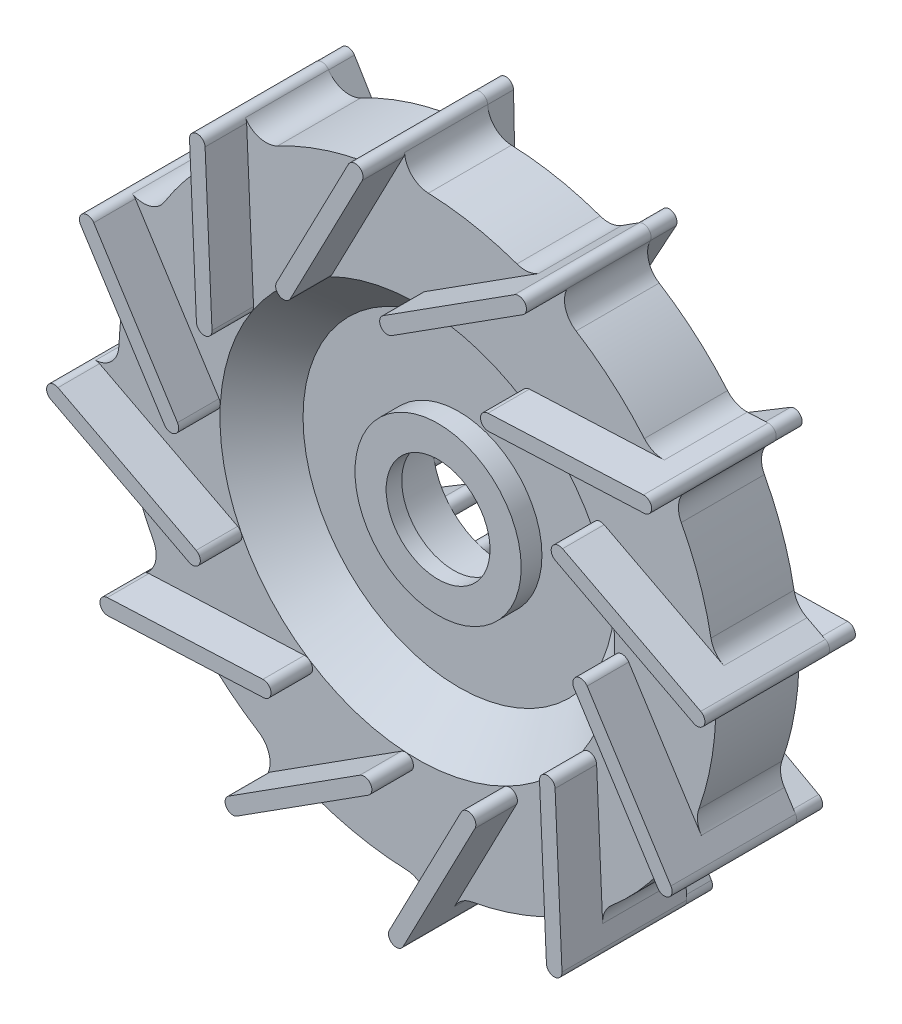
SolidWorks part; units mm, degrees
ref_plane "Front Plane" through (0, 0, 0) normal (1, 0, 0) x (0, 1, 0)
ref_plane "Top Plane" through (0, 0, 0) normal (0, 0, 1) x (0, 1, 0)
ref_plane "Right Plane" through (0, 0, 0) normal (0, 1, 0) x (-1, 0, 0)
sketch "Sketch1" plane through (0, 0, 0) normal (1, 0, 0) x (0, 1, 0)
  line L0 (13, -24) -> (13, -15)
  line L1 (13, -15) -> (10, -15)
  line L2 (10, -15) -> (10, -12)
  line L3 (10, -12) -> (16, -12)
  line L4 (16, -12) -> (16, -16)
  line L5 (16, -16) -> (30, -16)
  line L6 (30, -16) -> (38, -8)
  line L8 (63.5, 0) -> (63.5, -24)
  line L9 (63.5, -24) -> (13, -24)
  line L10 (0, 0) -> (0, -61.0212) construction
  line L11 (38, -8) -> (38, 0)
  line L12 (38, 0) -> (63.5, 0)
  point P14 (0, 0)
  dimension "D1" = 26
  dimension "D2" = 76
  dimension "D3" = 20
  dimension "D4" = 3
  dimension "D5" = 127
  dimension "D6" = 45
  dimension "D7" = 3
  dimension "D8" = 16
  dimension "D9" = 8
  dimension "D10" = 8
  dimension "D11" = 4
revolve "Revolve1" add sketch "Sketch1" angle 360 about L10
sketch "Sketch2" plane through (0, 0, 0) normal (0, 0, 1) x (1, 0, 0)
  line L0 (0, 38) -> (28.9858, 56.4984) construction
  line L1 (-63.5, 0) -> (-57.5, 0) construction
  line L2 (26.7084, 56.8244) -> (1.443, 40.7003)
  line L3 (3.0569, 38.1714) -> (28.3223, 54.2955)
  line L16 (27.5153, 55.5599) -> (4.5325, 13.7734) construction
  line L17 (28.8072, 54.8494) -> (5.8244, 13.0628)
  line L18 (3.2406, 14.484) -> (26.2234, 56.2705)
  circle A0 centre (0, 0) radius 38 construction
  circle A1 centre (0, 0) radius 38 construction
  circle A2 centre (0, 0) radius 63.5 construction
  arc A3 (1.443, 40.7003) -> (3.0569, 38.1714) centre (2.2499, 39.4359) ccw
  arc A4 (28.3223, 54.2955) -> (26.7084, 56.8244) centre (27.5153, 55.5599) ccw
  arc A21 (5.8244, 13.0628) -> (3.2406, 14.484) centre (4.5325, 13.7734) cw
  arc A22 (26.2234, 56.2705) -> (28.8072, 54.8494) centre (27.5153, 55.5599) cw
  circle A37 centre (0, 0) radius 38
  circle A38 centre (0, 0) radius 63.5
  circle A39 centre (0, 0) radius 57.5
  circle A40 centre (0, 0) radius 13.0256
  circle M5 centre (0, 0) radius 38
  circle M6 centre (0, 0) radius 63.5
  dimension "D2" = 3
  dimension "D1" = 6
extrude "Cut-Extrude1" cut sketch "Sketch2" against normal blind 8 contours A38 | A38 | A38 | A38 | A38 | A38 | L2 A39 L17 A3 M5 | L17 A39 L18 M5 | L18 A39 L3 A3 M5 | L3 A39 L2 A3 | L3 A39 L18 region at (12.0808, 45.6952, 0) region at (10.5142, 48.4188, 0) region at (24.0243, 51.7871, 0) region at (13.7332, 41.5708, 0) region at (20.6077, 42.9831, 0)
extrude "Cut-Extrude2" cut sketch "Sketch2<5>" against normal through all contours A39 L2 A4 L17 M6 | A39 L17 A4 L3 | A39 L3 A4 L17 A22 L18 | A39 L18 A22 L17 A4 L2 region at (24.0009, 54.141, 0) region at (52.4265, 32.5398, 0) region at (26.7307, 54.7087, 0) region at (26.642, 52.4627, 0)
sketch "Sketch2<5>" plane through (0, 0, 0) normal (0, 0, 1) x (1, 0, 0) same geometry as "Sketch2"
extrude "Boss-Extrude1" add sketch "Sketch2<6>" against normal up to surface (24 mm away) contours L18 A22 L17 A4 L2 A3 L3 | A22 L18 L3 A4 L17 | L3 A39 L2 A3 | L3 A39 L18 region at (24.0009, 54.141, 0) region at (12.0808, 45.6952, 0) region at (24.0243, 51.7871, 0) region at (26.7307, 54.7087, 0) up to face at (13, 0, -24)
sketch "Sketch2<6>" plane through (0, 0, 0) normal (0, 0, 1) x (1, 0, 0) same geometry as "Sketch2"
extrude "Boss-Extrude3" add sketch "Sketch2<9>" against normal blind 5 from surface contours L17 A39 L3 L18 M5 | A39 L3 A4 L17 A22 L18 | L3 A39 L18 | A39 L17 A4 L3 | A21 L17 L18 M5 region at (24.0243, 51.7871, 0) region at (26.7307, 54.7087, 0) region at (26.642, 52.4627, 0) region at (20.6077, 42.9831, 0) region at (9.9515, 23.6218, 0) starting at face at (14.0709, 27.9752, -24)
sketch "Sketch2<9>" plane through (0, 0, 0) normal (0, 0, 1) x (1, 0, 0) same geometry as "Sketch2"
fillet "Fillet1" radius 4.7625 2 edges at (21.3352, 53.3953, -16) (24.6468, 51.9498, -16)
pattern_circular "CirPattern1" count 12 over 360 about axis through (0, 0, 0) along (0, 0, 1) of "Fillet1", "Boss-Extrude1", "Boss-Extrude3" reverse direction yes
